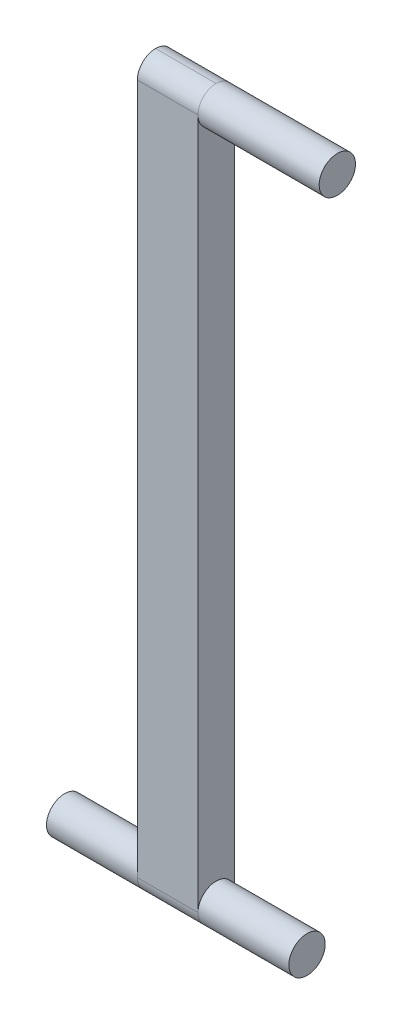
SolidWorks part; units mm, degrees
ref_plane "Front Plane" through (0, 0, 0) normal (0, 0, 1) x (1, 0, 0)
ref_plane "Top Plane" through (0, 0, 0) normal (0, 1, 0) x (1, 0, 0)
ref_plane "Right Plane" through (0, 0, 0) normal (1, 0, 0) x (0, 0, -1)
sketch "Sketch1" plane through (0, 0, 0) normal (0, 0, 1) x (1, 0, 0)
  line L1 (2.5, 30) -> (-2.5, 30)
  line L2 (2.5, 30) -> (2.5, -30)
  line L3 (2.5, -30) -> (-2.5, -30)
  line L4 (-2.5, 30) -> (-2.5, -30)
  line L5 (2.5, 30) -> (-2.5, -30) construction
  line L6 (2.5, -30) -> (-2.5, 30) construction
  point P0 (0, 0)
  dimension "D1" = 5
  dimension "D2" = 60
extrude "Boss-Extrude1" add sketch "Sketch1" along normal blind 3
sketch "Sketch2" plane through (2.5, 0, 0) normal (1, 0, 0) x (0, 0, -1)
  line L0 (-3, 30) -> (0, 30) construction
  line L1 (0, -30) -> (0, 30) construction
  line L2 (-3, -30) -> (-3, 30) construction
  circle A0 centre (-1.5, 28.5) radius 1.5
extrude "Boss-Extrude2" add sketch "Sketch2" along normal blind 10
fillet "Fillet1" radius 1.5 2 edges at (0, 30, 3) (0, 30, 0)
ref_plane "Plane1" through (0, 0, 0) normal (-1, 0, 0) x (0, 0, 1)
sketch "Sketch3" plane through (0, 0, 0) normal (-1, 0, 0) x (0, 0, 1)
  line L0 (0, 28.5) -> (0, -30) construction
  line L1 (3, -30) -> (3, 28.5) construction
  line L2 (3, -30) -> (0, -30) construction
  circle A0 centre (1.5, -28.5) radius 1.5
extrude "Boss-Extrude3" add sketch "Sketch3" along normal blind 10 and the other way blind 10
fillet "Fillet2" radius 1.5 2 edges at (0, -30, 3) (0, -30, 0)
